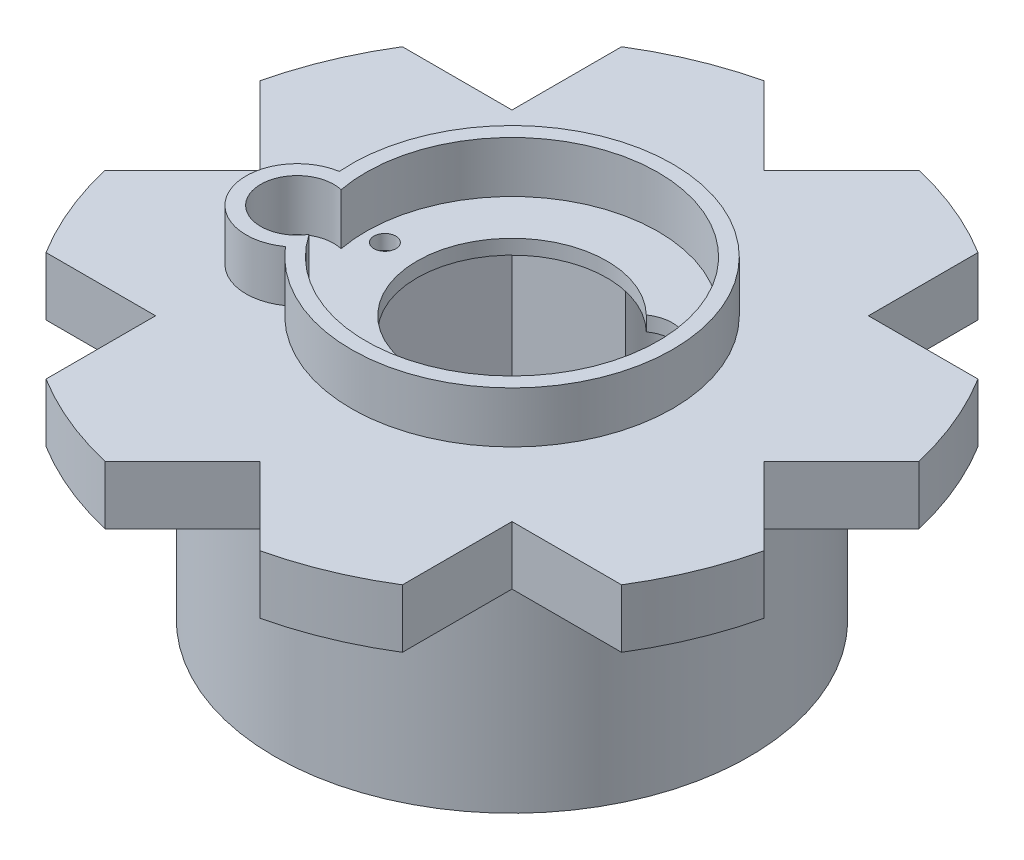
SolidWorks part; units mm, degrees
ref_plane "Front" through (0, 0, 0) normal (0, 0, 1) x (1, 0, 0)
ref_plane "Top" through (0, 0, 0) normal (0, 1, 0) x (1, 0, 0)
ref_plane "Right" through (0, 0, 0) normal (1, 0, 0) x (0, 0, -1)
sketch "Sketch2" plane through (0, 0, 0) normal (0, 0, 1) x (1, 0, 0)
  line L0 (13, 0) -> (13, 36)
  line L1 (13, 36) -> (22.5, 36)
  line L3 (22.5, 36) -> (32.5, 36)
  line L4 (32.5, 36) -> (32.5, 0)
  line L5 (32.5, 0) -> (13, 0)
  line L6 (0, 0) -> (0, 51.8689) construction
  dimension "D1" = 13
  dimension "D2" = 10
  dimension "D3" = 22.5
  dimension "D4" = 36
revolve "Revolve1" add sketch "Sketch2" angle 360 about L6
sketch "Sketch3" plane through (0, 36, 0) normal (0, 1, 0) x (1, 0, 0)
  line L0 (-17.4, 0) -> (17.4, 0) construction
  circle A0 centre (-17.4, 0) radius 1.5
  circle A1 centre (17.4, 0) radius 1.5
  dimension "D2" = 3
  dimension "D1" = 17.4
extrude "Cut-Extrude1" cut sketch "Sketch3" against normal blind 20
sketch "Sketch4" plane through (0, 0, 0) normal (0, 1, 0) x (1, 0, 0)
  line L0 (0, 34.5) -> (-10.6066, 45.1066)
  line L1 (0, 34.5) -> (10.6066, 45.1066)
  line L2 (0, 34.5) -> (0, 0) construction
  line L3 (17.7324, 42.8097) -> (12.4372, 30.0261)
  line L5 (-17.7324, 42.8097) -> (-12.4372, 30.0261)
  line L6 (-12.4372, 30.0261) -> (0, 0) construction
  line L7 (0, 0) -> (12.4372, 30.0261) construction
  circle A0 centre (0, 0) radius 32.5 construction
  arc A1 (12.4372, 30.0261) -> (-12.4372, 30.0261) centre (0, 0) ccw
  arc A2 (17.7324, 42.8097) -> (10.6066, 45.1066) centre (0, 0) ccw
  arc A3 (-10.6066, 45.1066) -> (-17.7324, 42.8097) centre (0, 0) ccw
  arc A4 (13.2026, 31.8738) -> (-13.2026, 31.8738) centre (0, 0) ccw construction
  dimension "D1" = 90
  dimension "D2" = 15
  dimension "D3" = 45
  dimension "D4" = 2
extrude "Boss-Extrude2" add sketch "Sketch4" against normal blind 8 from vertex contours L5 A1 L3 A2 L1 L0 A3 starting at point (13, 36, 0)
ref_axis "Axis1" through (0, 50, 0) along (0, -1, 0)
pattern_circular "CirPattern1" count 8 over 360 about axis through (0, 50, 0) along (0, -1, 0) of "Boss-Extrude2"
sketch "Sketch5" plane through (0, 36, 0) normal (0, 1, 0) x (1, 0, 0)
  circle A0 centre (11.7919, 5.4728) radius 4.6699
  circle A1 centre (0, 0) radius 13 construction
extrude "Cut-Extrude2" cut sketch "Sketch5" against normal through all
sketch "Sketch6" plane through (0, 0, 0) normal (0, -1, 0) x (1, 0, 0)
  circle A0 centre (0, 0) radius 34.3369
  circle A2 centre (0, 0) radius 64.3369
  arc A4 (10.6066, -45.1066) -> (24.3952, -39.3952) centre (0, 0) ccw construction
  dimension "D1" = 12
  dimension "D2" = 30
extrude "Cut-Extrude3" [suppressed] cut sketch "Sketch6" against normal offset from surface (18 mm away) 1 from offset 1 offset against normal yes
sketch "Sketch7" plane through (0, 0, 0) normal (0, 0, 1) x (1, 0, 0)
  line L0 (35, 20) -> (35, 19)
  line L2 (35, 19) -> (23.9031, 18.25)
  line L3 (23.9031, 18.25) -> (23.9031, 17.75)
  line L4 (23.9031, 17.75) -> (35, 17)
  line L5 (35, 17) -> (35, 16)
  line L6 (35, 16) -> (45, 16)
  line L7 (45, 16) -> (45, 20)
  line L8 (45, 20) -> (35, 20)
  line L9 (23.9031, 18) -> (45, 18) construction
  line L12 (39.3952, 28) -> (45.1066, 28) construction
  dimension "D1" = 1
  dimension "D2" = 0.5
  dimension "D3" = 2
  dimension "D4" = 4
  dimension "D5" = 10
  dimension "D6" = 35
revolve "Cut-Revolve1" [suppressed] cut sketch "Sketch7" angle 360 about axis through (0, 50, 0) along (0, -1, 0)
fillet "Fillet2" [suppressed] radius 12
sketch "Sketch8" plane through (0, 0, 0) normal (0, -1, 0) x (1, 0, 0)
  line L0 (-19.5, 19.5) -> (19.5, 19.5)
  line L1 (-19.5, 19.5) -> (-19.5, -19.5)
  line L2 (19.5, 19.5) -> (19.5, -19.5)
  line L3 (-19.5, -19.5) -> (-4, -19.5)
  line L4 (-19.5, 19.5) -> (19.5, -19.5) construction
  line L5 (4, -19.5) -> (19.5, -19.5)
  arc A0 (-4, -19.5) -> (4, -19.5) centre (0, -19.5) ccw
  dimension "D3" = 8
  dimension "D1" = 39
  dimension "D2" = 39
extrude "Cut-Extrude4" cut sketch "Sketch8" against normal blind 34 draft 0.5 contours L0 L2 L5 A0 L3 L1
sketch "Sketch9" plane through (0, 36, 0) normal (0, 1, 0) x (1, 0, 0)
  arc A0 (-16.7151, -14.304) -> (-21.9338, -1.7049) centre (0, 0) ccw
  arc A1 (-21.9338, -1.7049) -> (-16.7151, -14.304) centre (-20.7873, -8.6104) ccw
  arc A2 (-16.8025, -14.9642) -> (-22.4624, -1.2998) centre (0, 0) ccw construction
  arc A4 (-22.4624, -1.2998) -> (-16.8025, -14.9642) centre (-20.7873, -8.6104) ccw construction
  arc A5 (-19.6468, -3.7422) -> (-16.5385, -11.2462) centre (-20.7873, -8.6104) ccw
  arc A6 (-16.5385, -11.2462) -> (-19.6468, -3.7422) centre (0, 0) ccw
  dimension "D1" = 0.5
  dimension "D2" = 0.5
  dimension "D3" = 2
extrude "Boss-Extrude3" add sketch "Sketch9" along normal blind 7 contours A0 A1 | A6 A5
